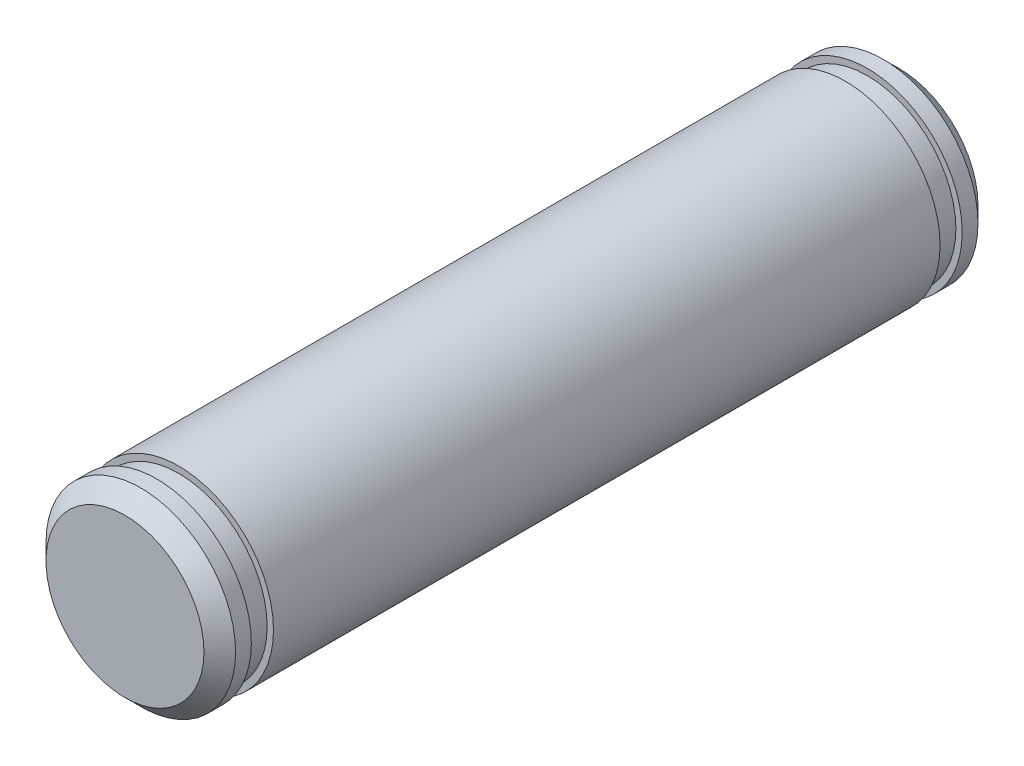
SolidWorks part; units mm, degrees
material "Chromowa stal nierdzewna"
ref_plane "Płaszczyzna przednia" through (0, 0, 0) normal (0, 0, 1) x (1, 0, 0)
ref_plane "Płaszczyzna górna" through (0, 0, 0) normal (0, 1, 0) x (1, 0, 0)
ref_plane "Płaszczyzna prawa" through (0, 0, 0) normal (1, 0, 0) x (0, 0, -1)
sketch "Szkic1" plane through (0, 0, 0) normal (0, 0, 1) x (1, 0, 0)
  circle A0 centre (0, 0) radius 3
  dimension "D1" = 6
extrude "Dodanie-wyciągnięcie1" add sketch "Szkic1" along normal blind 24.5
chamfer "Sfazowanie1" distance 0.5 angle 45 2 edges at (3, 0, 0) (3, 0, 24.5)
sketch "Szkic2" plane through (0, 0, 24.5) normal (0, 0, 1) x (1, 0, 0)
  circle A0 centre (0, 0) radius 3
  circle A1 centre (0, 0) radius 2.8
  dimension "D1" = 6
  dimension "D2" = 5.6
extrude "Wytnij-wyciągnięcie1" cut sketch "Szkic2" against normal blind 0.7 from offset 1 offset against normal yes
sketch "Szkic3" plane through (0, 0, 0) normal (0, 0, -1) x (-1, 0, 0)
  circle A0 centre (0, 0) radius 2.8
  circle A1 centre (0, 0) radius 3
  dimension "D1" = 6
  dimension "D2" = 5.6
extrude "Wytnij-wyciągnięcie2" cut sketch "Szkic3" against normal blind 0.7 from offset 1 offset against normal yes
